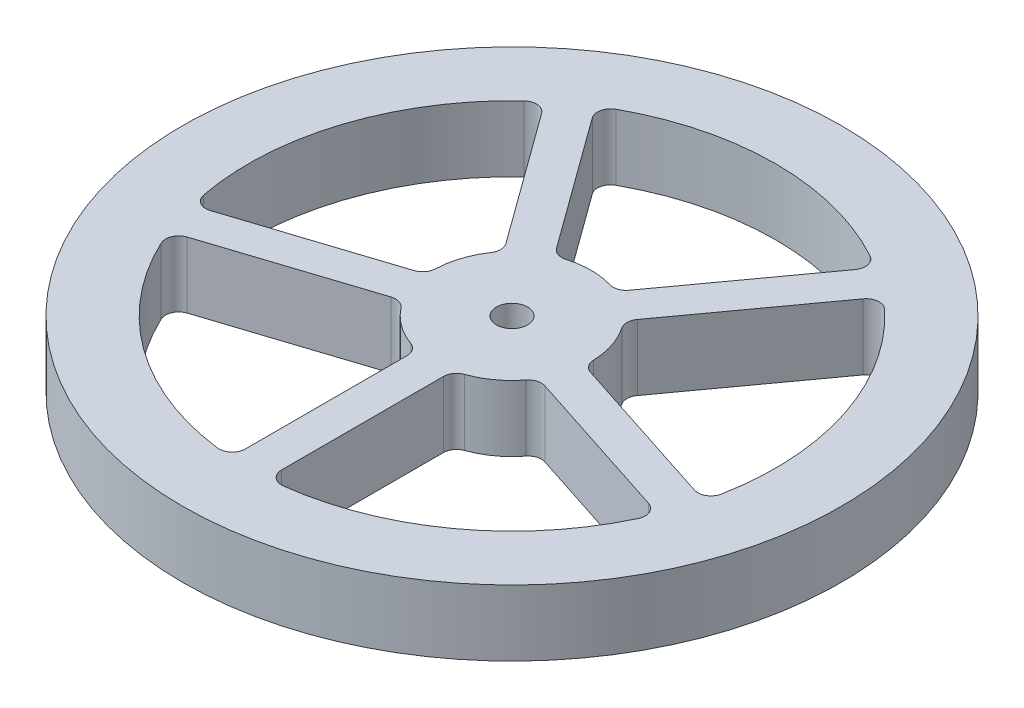
SolidWorks part; units mm, degrees
material "Nylon 6/10"
ref_plane "Front Plane" through (0, 0, 0) normal (0, 0, 1) x (1, 0, 0)
ref_plane "Top Plane" through (0, 0, 0) normal (0, 1, 0) x (1, 0, 0)
ref_plane "Right Plane" through (0, 0, 0) normal (1, 0, 0) x (0, 0, -1)
sketch "Sketch1" plane through (0, 0, 0) normal (0, 1, 0) x (1, 0, 0)
  circle A0 centre (0, 0) radius 31.75
  circle A1 centre (0, 0) radius 1.5
  dimension "D1" = 63.5
  dimension "D2" = 3
extrude "Boss-Extrude1" add sketch "Sketch1" along normal blind 6.35
sketch "Sketch2" plane through (0, 6.35, 0) normal (0, 1, 0) x (1, 0, 0)
  circle A0 centre (0, 0) radius 7.62
  circle A1 centre (0, 0) radius 25.4
  circle A3 centre (0, 0) radius 31.75 construction
  dimension "D1" = 15.24
  dimension "D2" = 6.35
extrude "Cut-Extrude1" cut sketch "Sketch2" against normal up to surface (6.35 mm away) up to face at (0, 0, 31.75)
sketch "Sketch3" plane through (0, 6.35, 0) normal (0, 1, 0) x (1, 0, 0)
  line L0 (-1.7462, -8.3627) -> (-1.7462, -23.9407)
  line L1 (1.7462, -8.3627) -> (1.7462, -23.9407)
  line L3 (0, -7.62) -> (0, -25.4) construction
  line L4 (-1.7462, -16.1517) -> (0, -16.51) construction
  line L5 (0, -16.51) -> (1.7462, -16.1517) construction
  circle A0 centre (0, 0) radius 7.62 construction
  circle A1 centre (0, 0) radius 25.4 construction
  arc A2 (-3.175, -25.2008) -> (3.175, -25.2008) centre (0, 0) ccw
  arc A3 (-2.5854, -7.168) -> (2.5854, -7.168) centre (0, 0) ccw
  arc A4 (-3.175, -25.2008) -> (-1.7462, -23.9407) centre (-3.0162, -23.9407) ccw
  arc A5 (1.7462, -23.9407) -> (3.175, -25.2008) centre (3.0162, -23.9407) ccw
  arc A6 (-2.5854, -7.168) -> (-1.7462, -8.3627) centre (-3.0162, -8.3627) cw
  arc A7 (1.7462, -8.3627) -> (2.5854, -7.168) centre (3.0162, -8.3627) cw
  dimension "D3" = 1.27
  dimension "D4" = 1.27
  dimension "D5" = 1.27
  dimension "D2" = 6.35
extrude "Boss-Extrude2" add sketch "Sketch3" against normal up to surface (6.35 mm away) contours L0 A4 A2 A5 L1 A7 A3 A6 up to face at (0, 0, 25.4)
ref_axis "Axis1" through (0, 6.35, 0) along (0, -1, 0)
pattern_circular "CirPattern1" count 5 over 360 about axis through (0, 6.35, 0) along (0, -1, 0) of "Boss-Extrude2"
ref_plane "Plane1" through (0, 3.175, 0) normal (0, 1, 0) x (1, 0, 0)
